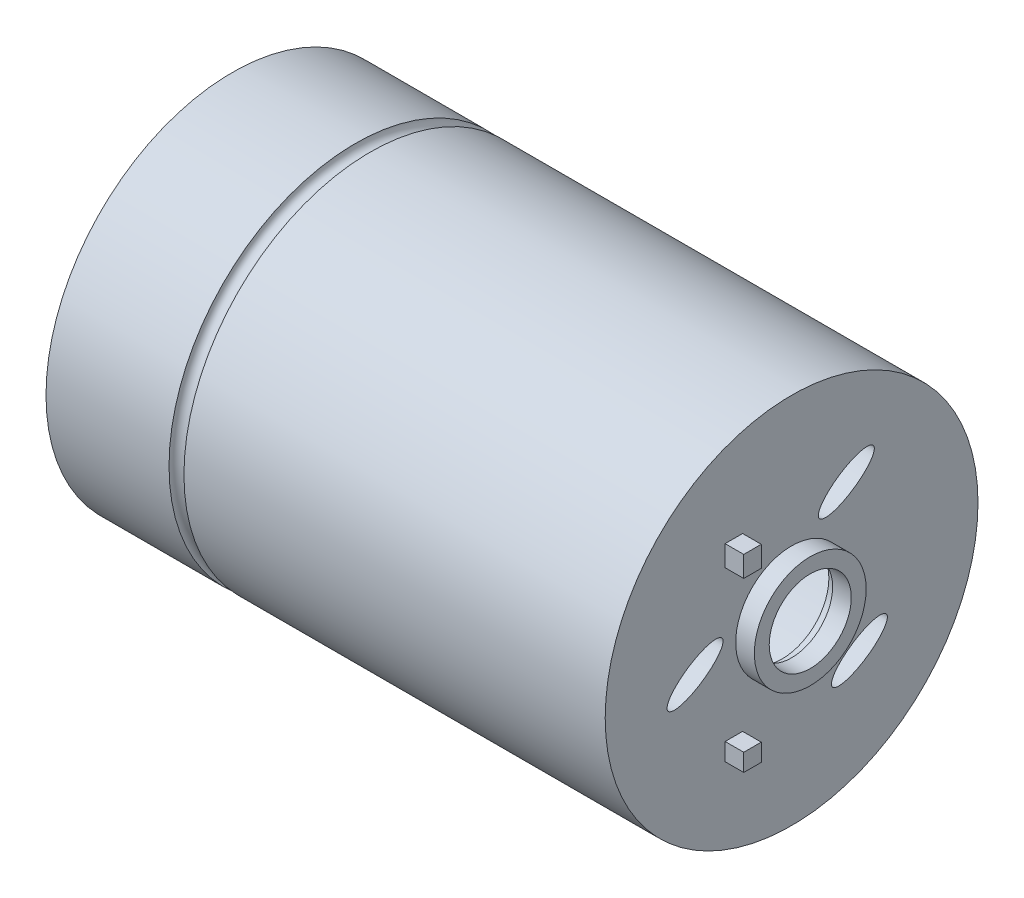
SolidWorks part; units mm, degrees
ref_plane "Front Plane" through (0, 0, 0) normal (1, 0, 0) x (0, 1, 0)
ref_plane "Top Plane" through (0, 0, 0) normal (0, 0, 1) x (0, 1, 0)
ref_plane "Right Plane" through (0, 0, 0) normal (0, 1, 0) x (-1, 0, 0)
sketch "Sketch1" plane through (0, 0, 0) normal (1, 0, 0) x (0, 1, 0)
  circle A0 centre (0, 0) radius 10
  dimension "D1" = 20
extrude "Boss-Extrude1" add sketch "Sketch1" along normal mid plane 30
sketch "Sketch2" plane through (15, 0, 0) normal (1, 0, 0) x (0, 1, 0)
  line L1 (-5.2451, 3.5675) -> (-4.3056, 3.5675)
  line L2 (-5.2451, 3.5675) -> (-5.2451, 2.6281)
  line L3 (-5.2451, 2.6281) -> (-4.3056, 2.6281)
  line L4 (-4.3056, 3.5675) -> (-4.3056, 2.6281)
  line L5 (-5.2451, 3.5675) -> (-4.3056, 2.6281) construction
  line L6 (-5.2451, 2.6281) -> (-4.3056, 3.5675) construction
  line L7 (3.7688, 3.5675) -> (4.8872, 3.5675)
  line L8 (3.7688, 3.5675) -> (3.7688, 2.6281)
  line L9 (3.7688, 2.6281) -> (4.8872, 2.6281)
  line L10 (4.8872, 3.5675) -> (4.8872, 2.6281)
  line L11 (3.7688, 3.5675) -> (4.8872, 2.6281) construction
  line L12 (3.7688, 2.6281) -> (4.8872, 3.5675) construction
  point P0 (-4.7753, 3.0978)
  point P5 (4.328, 3.0978)
extrude "Boss-Extrude2" add sketch "Sketch2" along normal blind 1
sketch "Sketch3" plane through (-15, 0, 0) normal (-1, 0, 0) x (0, -1, 0)
  circle A0 centre (0, 0) radius 2
  circle A1 centre (0, 0) radius 3
  dimension "D1" = 4
  dimension "D2" = 6
extrude "Boss-Extrude3" add sketch "Sketch3" along normal blind 2
sketch "Sketch4" plane through (15, 0, 0) normal (1, 0, 0) x (0, 1, 0)
  circle A0 centre (0, 0) radius 2
  circle A1 centre (0, 0) radius 3
  dimension "D1" = 4
  dimension "D2" = 6
extrude "Boss-Extrude4" add sketch "Sketch4" along normal blind 1
sketch "Sketch5" plane through (15, 0, 0) normal (1, 0, 0) x (0, 1, 0)
  ellipse E0 centre (-0.3958, 5.179) end of major axis (0.5633, 3.7176) minor radius 0.6318
  ellipse E1 centre (-3.6823, -3.6378) end of major axis (-2.7232, -5.0993) minor radius 0.6318
  ellipse E3 centre (4.4999, -2.9352) end of major axis (3.5408, -1.4737) minor radius 0.6318
extrude "Cut-Extrude1" cut sketch "Sketch5" against normal blind 1
shell "Shell4" thickness 0.5 removed face at (-15, 0, 2) removed face at (14, 0.5633, 3.7176) removed face at (14, -2.7232, -5.0993) removed face at (14, 5.459, -4.3966) removed face at (15, 0, -2)
sketch "Sketch6" plane through (-17, 0, 0) normal (-1, 0, 0) x (0, -1, 0)
  circle A0 centre (0, 0) radius 2.2016
extrude "Cut-Extrude2" cut sketch "Sketch6" against normal through all
ref_plane "Plane1" through (-8, 0, 0) normal (-1, 0, 0) x (0, -1, 0)
sketch "Sketch7" plane through (-8, 0, 0) normal (-1, 0, 0) x (0, -1, 0)
  circle A0 centre (0, 0) radius 10 construction
  circle A1 centre (0, 0) radius 10
sweep "Cut-Sweep1" cut path "Sketch7" circular profile diameter 0.8 parameters "D3"=0.8
